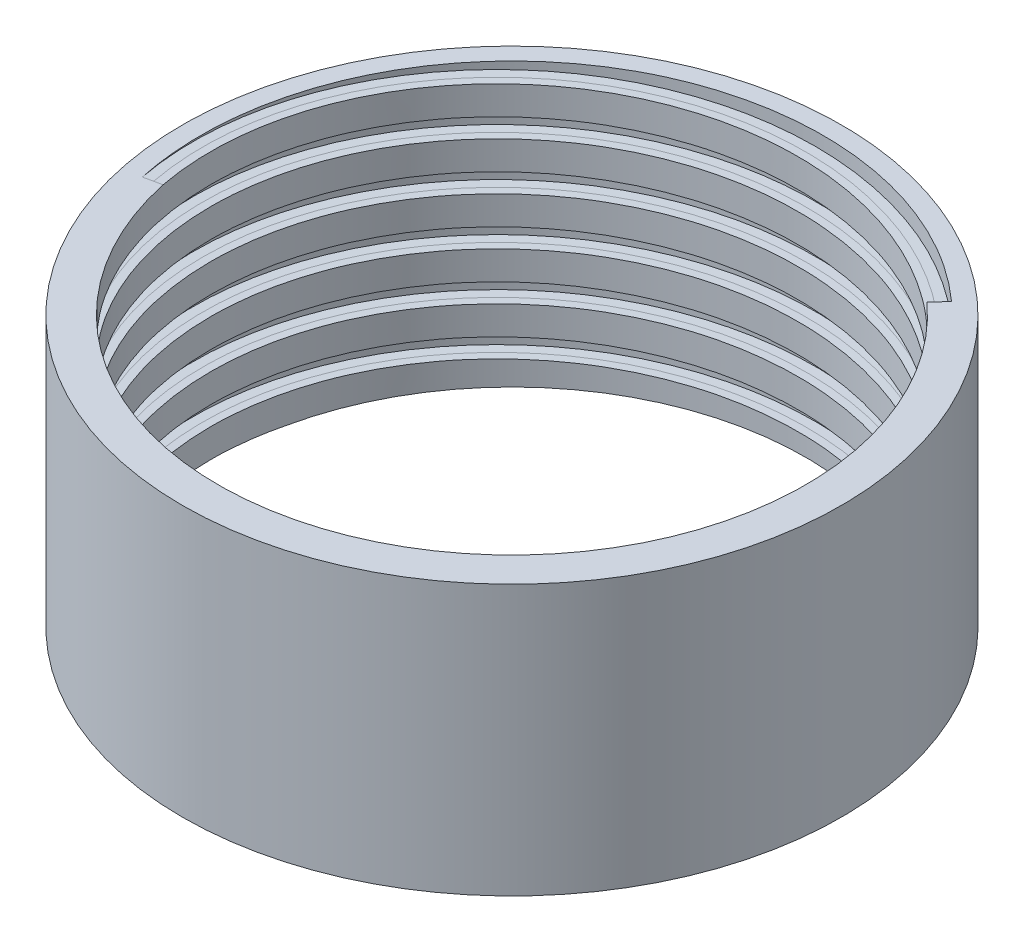
SolidWorks part; units mm, degrees
ref_plane "Front Plane" through (0, 0, 0) normal (0, 0, 1) x (1, 0, 0)
ref_plane "Top Plane" through (0, 0, 0) normal (0, 1, 0) x (1, 0, 0)
ref_plane "Right Plane" through (0, 0, 0) normal (1, 0, 0) x (0, 0, -1)
sketch "Sketch1" plane through (0, 0, 0) normal (0, 1, 0) x (1, 0, 0)
  circle A0 centre (0, 0) radius 18.5
  circle A1 centre (0, 0) radius 20.75
  dimension "D1" = 37
  dimension "D2" = 41.5
extrude "Boss-Extrude1" add sketch "Sketch1" along normal blind 17
ref_plane "Plane1" through (0, 22, 0) normal (0, 1, 0) x (1, 0, 0)
sketch "Sketch3" plane through (0, 22, 0) normal (0, 1, 0) x (1, 0, 0)
  circle A0 centre (0, 0) radius 18.5 construction
  circle A1 centre (0, 0) radius 18.5
curve "Helix/Spiral1" pitch 3 height 24 radius 18.5 centre (0, 22, 0) axis (0, -1, 0) start towards (1, 0, 0)
sketch "Sketch5" plane through (0, 0, 0) normal (0, 0, 1) x (1, 0, 0)
  line L0 (0, 0) -> (0, 38.7915) construction
  line L1 (22.825, 22) -> (-22.825, 22) construction
  line L2 (19, 22.6) -> (17, 22.6)
  line L3 (17, 22.6) -> (17, 21.4)
  line L4 (17, 21.4) -> (19, 21.4)
  line L5 (19.6, 22.6) -> (19.6, 21.4)
  line L6 (19.6, 21.4) -> (19, 21.4)
  line L7 (19, 22.6) -> (19.6, 22.6)
  arc A0 (19, 21.4) -> (19, 22.6) centre (19, 22) ccw construction
  dimension "D2" = 1.2
  dimension "D1" = 19
  dimension "D3" = 2
sweep "Cut-Sweep1" cut profiles "Sketch5" path "Helix/Spiral1"
ref_axis "Axis1" through (0, 27.723, 0) along (0, -1, 0)
